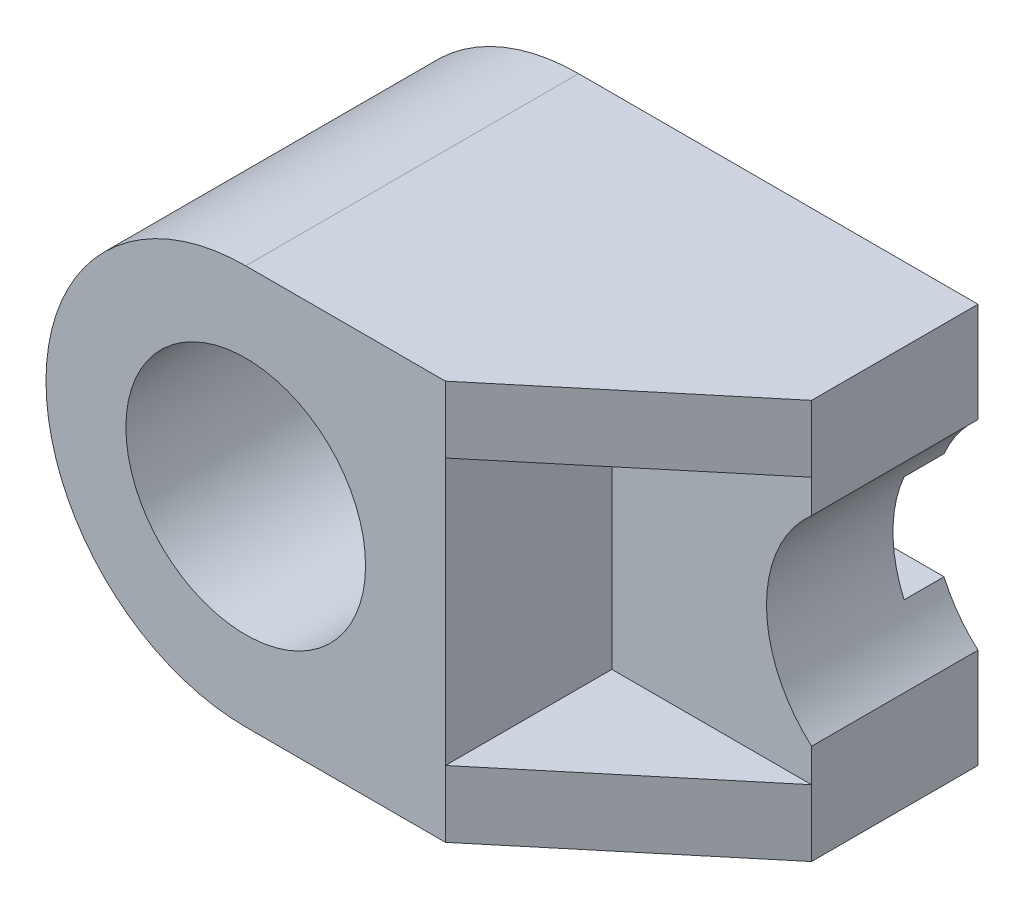
SolidWorks part; units mm, degrees
ref_plane "Front Plane" through (0, 0, 0) normal (0, 0, 1) x (1, 0, 0)
ref_plane "Top Plane" through (0, 0, 0) normal (0, 1, 0) x (1, 0, 0)
ref_plane "Right Plane" through (0, 0, 0) normal (1, 0, 0) x (0, 0, -1)
sketch "Sketch1" plane through (0, 0, 0) normal (0, 0, 1) x (1, 0, 0)
  line L0 (0, 30) -> (30, 30)
  line L1 (30, 30) -> (30, -30)
  line L2 (30, -30) -> (0, -30)
  arc A0 (0, -30) -> (0, 30) centre (0, 0) cw
  circle A1 centre (0, 0) radius 18
extrude "Boss-Extrude1" add sketch "Sketch1" against normal blind 50
sketch "Sketch2" plane through (0, 0, -50) normal (0, 0, -1) x (-1, 0, 0)
  line L0 (-30, -30) -> (-60, -30)
  line L1 (-30, 30) -> (-60, 30)
  line L2 (-60, 30) -> (-60, 15)
  line L3 (-60, -30) -> (-60, -15)
  line L4 (-30, 30) -> (-30, -30)
  line L7 (0, 30) -> (-30, 30)
  line L8 (-30, 30) -> (-30, -30)
  line L9 (-30, -30) -> (0, -30)
  line L10 (0, 30) -> (-30, 30)
  line L12 (-30, -30) -> (0, -30)
  arc A1 (-60, 15) -> (-60, -15) centre (-73.2288, 0) cw
  arc A3 (0, -30) -> (0, 30) centre (0, 0) ccw
  arc A4 (0, -30) -> (0, 30) centre (0, 0) ccw
  line M8 (-30, 30) -> (-30, -30)
  dimension "D1" = 15
  dimension "D3" = 30
  dimension "D6" = 0
  dimension "D2" = 15
  dimension "D4" = 30
  dimension "D5" = 20
extrude "Boss-Extrude3" add sketch "Sketch2" against normal blind 25 contours L2 A1 L3 L0 L1 M8 region at (43.9607, 0, -50)
sketch "Sketch6" plane through (0, 30, 0) normal (0, 1, 0) x (1, 0, 0)
  line L1 (60, 25) -> (30, 0)
  line L2 (30, 0) -> (30, 25)
  line L3 (30, 25) -> (60, 25)
extrude "Boss-Extrude4" add sketch "Sketch6" against normal blind 10 contours L1 L2 L3
sketch "Sketch11" plane through (0, -30, 0) normal (0, -1, 0) x (-1, 0, 0)
  line L0 (-30, 0) -> (-30, 25)
  line L1 (-30, 25) -> (-60, 25)
  line L2 (-60, 25) -> (-30, 0)
extrude "Boss-Extrude5" add sketch "Sketch11" against normal blind 10
sketch "Sketch12" plane through (0, 0, -50) normal (0, 0, -1) x (-1, 0, 0)
  line L1 (-53.2288, 0) -> (-53.2288, 8) construction
  line L2 (-54.8985, 8) -> (-16.1245, 8)
  line L5 (28.9137, 8) -> (16.1245, 8)
  line L6 (-53.2288, 0) -> (-53.2288, -8) construction
  line L7 (-54.8985, -8) -> (-16.1245, -8)
  line L8 (16.1245, -8) -> (28.9137, -8)
  arc A0 (-60, -15) -> (-60, 15) centre (-73.2288, 0) ccw construction
  arc A1 (0, -30) -> (0, 30) centre (0, 0) ccw construction
  circle A2 centre (0, 0) radius 18 construction
  arc A3 (-16.1245, 8) -> (-16.1245, -8) centre (0, 0) ccw
  arc A4 (16.1245, 8) -> (16.1245, -8) centre (0, 0) ccw
  arc A5 (28.9137, 8) -> (28.9137, -8) centre (0, 0) cw
  point P27 (0, 0)
  circle M10 centre (0, 0) radius 18
  arc M14 (-60, 15) -> (-60, -15) centre (-73.2288, 0) cw
  dimension "D1" = 16
  dimension "D2" = 16
extrude "Cut-Extrude2" cut sketch "Sketch12" against normal blind 6 contours A5 L8 A4 L5
extrude "Cut-Extrude3" cut sketch "Sketch12<8>" against normal blind 6 contours L7 L2 M14 M10 region at (35.5812, 0, -50)
sketch "Sketch12<8>" plane through (0, 0, -50) normal (0, 0, -1) x (-1, 0, 0) same geometry as "Sketch12"
